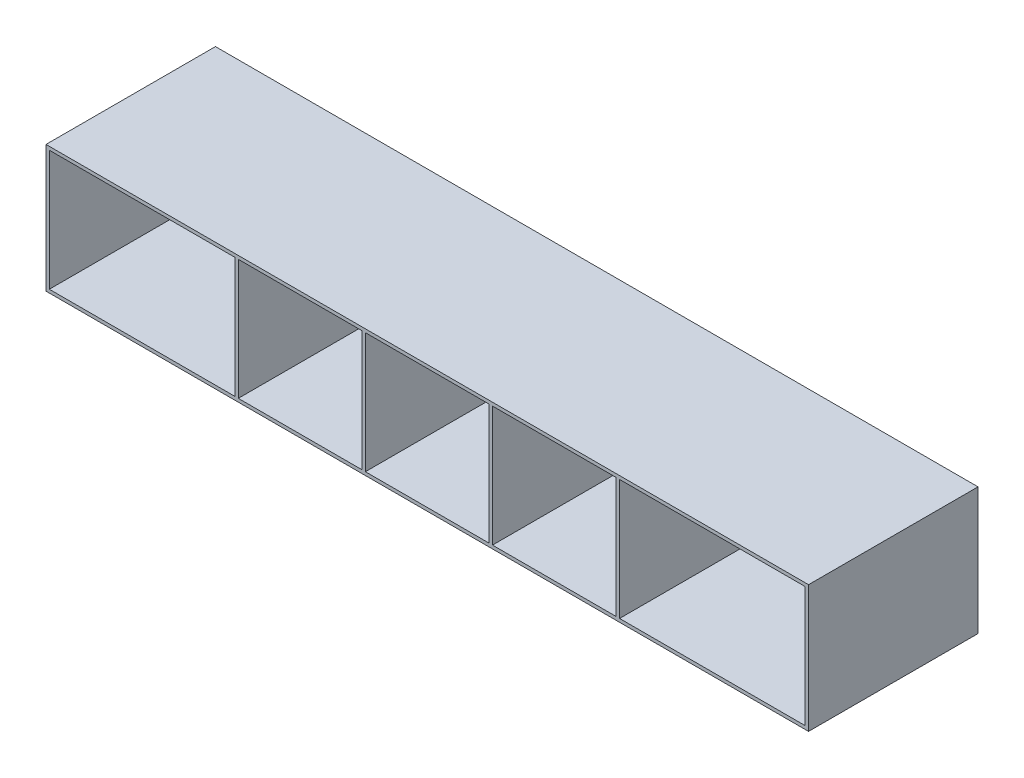
SolidWorks part; units mm, degrees
ref_plane "Спереди" through (0, 0, 0) normal (0, 0, 1) x (1, 0, 0)
ref_plane "Сверху" through (0, 0, 0) normal (0, 1, 0) x (1, 0, 0)
ref_plane "Справа" through (0, 0, 0) normal (1, 0, 0) x (0, 0, -1)
sketch "Эскиз3" plane through (0, 0, 0) normal (0, 0, 1) x (1, 0, 0)
  line L0 (-226.6, -36.1) -> (226.6, -36.1)
  line L1 (-228.6, 38.1) -> (228.6, 38.1)
  line L2 (-228.6, 38.1) -> (-228.6, -38.1)
  line L3 (-228.6, -38.1) -> (228.6, -38.1)
  line L4 (228.6, 38.1) -> (228.6, -38.1)
  line L5 (-228.6, 38.1) -> (228.6, -38.1) construction
  line L6 (-228.6, -38.1) -> (228.6, 38.1) construction
  line L7 (226.6, 36.1) -> (226.6, -36.1)
  line L8 (-226.6, 36.1) -> (226.6, 36.1)
  line L9 (-226.6, 36.1) -> (-226.6, -36.1)
  line L10 (-37.1, -38.1) -> (-37.1, 38.1)
  line L11 (-113.3, -38.1) -> (-115.3, -38.1)
  line L12 (-113.3, -38.1) -> (-113.3, 38.1)
  line L13 (-113.3, 38.1) -> (-115.3, 38.1)
  line L14 (-115.3, -38.1) -> (-115.3, 38.1)
  line L15 (-113.3, -38.1) -> (-115.3, 38.1) construction
  line L16 (-1, 38.1) -> (1, -38.1) construction
  line L17 (-113.3, 38.1) -> (-115.3, -38.1) construction
  line L18 (-37.1, 38.1) -> (-39.1, 38.1)
  line L19 (-39.1, -38.1) -> (-39.1, 38.1)
  line L20 (-37.1, -38.1) -> (-39.1, -38.1)
  line L21 (39.1, -38.1) -> (39.1, 38.1)
  line L22 (39.1, 38.1) -> (37.1, 38.1)
  line L23 (37.1, -38.1) -> (37.1, 38.1)
  line L24 (39.1, -38.1) -> (37.1, -38.1)
  line L25 (115.3, -38.1) -> (115.3, 38.1)
  line L26 (115.3, 38.1) -> (113.3, 38.1)
  line L27 (113.3, -38.1) -> (113.3, 38.1)
  line L28 (115.3, -38.1) -> (113.3, -38.1)
  point P0 (0, 0)
  point P10 (-114.3, 0)
  point P12 (0, 0)
  dimension "D1" = 457.2
  dimension "D2" = 76.2
  dimension "D4" = 2
  dimension "D3" = 2
  dimension "D5" = 4
extrude "Бобышка-Вытянуть4" add sketch "Эскиз3" along normal blind 101.6 contours L3 L4 L1 L2
extrude "Вырез-Вытянуть2" cut sketch "Эскиз3<3>" along normal through all contours L25 L8 L9 L0 | L8 L27 L0 L21 | L8 L23 L0 | L8 L19 L0 | L8 L0 L7 region at (-170.95, 0, 0) region at (-76.2, 0, 0) region at (0, 0, 0) region at (76.2, 0, 0) region at (170.95, 0, 0)
sketch "Эскиз3<3>" plane through (0, 0, 0) normal (0, 0, 1) x (1, 0, 0) same geometry as "Эскиз3"
